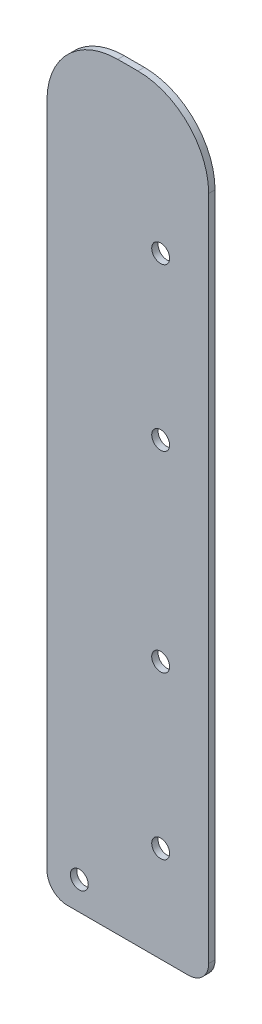
SolidWorks part; units mm, degrees
ref_plane "Front Plane" through (0, 0, 0) normal (0, 0, 1) x (1, 0, 0)
ref_plane "Top Plane" through (0, 0, 0) normal (0, 1, 0) x (1, 0, 0)
ref_plane "Right Plane" through (0, 0, 0) normal (1, 0, 0) x (0, 0, -1)
sketch "Sketch1" plane through (0, 0, 0) normal (0, 0, 1) x (1, 0, 0)
  line L1 (0, -146.6506) -> (0, 146.6506) construction
  line L3 (40.64, 5.08) -> (40.64, 172.72)
  line L5 (35.56, 0) -> (28.575, 0)
  line L7 (66.681, 0) -> (66.681, 88.9) construction
  line L8 (28.575, 0) -> (40.64, 0) construction
  line L9 (28.575, 177.8) -> (28.575, 0) construction
  line L10 (118.1346, 0) -> (-118.1346, 0) construction
  line L11 (66.681, 88.9) -> (0, 88.9) construction
  line L14 (28.575, 0) -> (5.08, 0)
  line L18 (66.681, 88.9) -> (66.681, 177.8) construction
  line L19 (66.681, 177.8) -> (0, 177.8) construction
  line L20 (0, 5.08) -> (0, 172.72)
  line L23 (28.575, 0) -> (20.32, 0) construction
  line L24 (20.32, 0) -> (20.4578, 177.8) construction
  line L25 (20.32, 0) -> (14.732, 0) construction
  line L26 (14.732, 0) -> (14.732, 8.89) construction
  line L27 (14.732, 8.89) -> (14.732, 177.8) construction
  line L28 (28.575, 24.13) -> (0, 24.13) construction
  line L35 (20.32, 0) -> (17.6513, 0) construction
  line L46 (17.78, 190.5) -> (22.86, 190.5)
  line L47 (20.4578, 177.8) -> (20.4578, 190.5) construction
  line L48 (20.4442, 160.274) -> (20.4578, 190.5) construction
  line L49 (20.4578, 190.5) -> (-14.4304, 190.5) construction
  line L50 (20.4442, 160.274) -> (0, 160.274) construction
  line L51 (40.64, 10.2129) -> (38.1, 10.2129) construction
  line L52 (38.1, 10.2129) -> (38.1, 0.6806) construction
  line L53 (38.1, 0.6806) -> (38.1, 181.8781) construction
  circle A0 centre (28.575, 24.13) radius 2.2479
  circle A1 centre (28.575, 64.77) radius 2.2479
  arc A5 (35.56, 0) -> (40.64, 5.08) centre (35.56, 5.08) ccw
  arc A6 (5.08, 0) -> (0, 5.08) centre (5.08, 5.08) cw
  circle A7 centre (28.575, 113.03) radius 2.2479
  circle A8 centre (28.575, 153.67) radius 2.2479
  arc A13 (40.64, 172.72) -> (22.86, 190.5) centre (22.86, 172.72) ccw
  arc A14 (0, 172.72) -> (17.78, 190.5) centre (17.78, 172.72) cw
  circle A15 centre (8.128, 7.112) radius 2.2479
  point P24 (0, 190.5)
  point P30 (0, 0)
  point P38 (0, 190.5)
  point P42 (0, 185.42)
  point P46 (40.64, 185.0608)
  point P52 (0, 190.5)
  dimension "D7" = 4.4958
  dimension "D5" = 24.13
  dimension "D6" = 4.4958
  dimension "D9" = 24.13
  dimension "D11" = 88.9
  dimension "D12" = 5.08
  dimension "D13" = 4.4958
  dimension "D15" = 4.4958
  dimension "D17" = 4.4958
  dimension "D19" = 17.78
  dimension "D26" = 2.54
  dimension "D20" = 32.512
  dimension "D25" = 12.7
  dimension "D27" = 9.525
  dimension "D1" = 190.5
  dimension "D2" = 40.64
  dimension "D3" = 88.9
  dimension "D4" = 9.525
  dimension "D8" = 40.64
  dimension "D10" = 24.13
  dimension "D14" = 7.112
  dimension "D16" = 40.64
  dimension "D18" = 24.13
  dimension "D21" = 30.226
  dimension "D23" = 20.32
  dimension "D24" = 25.908
  dimension "D28" = 64.77
extrude "Boss-Extrude2" add sketch "Sketch1" along normal blind 1.6002
